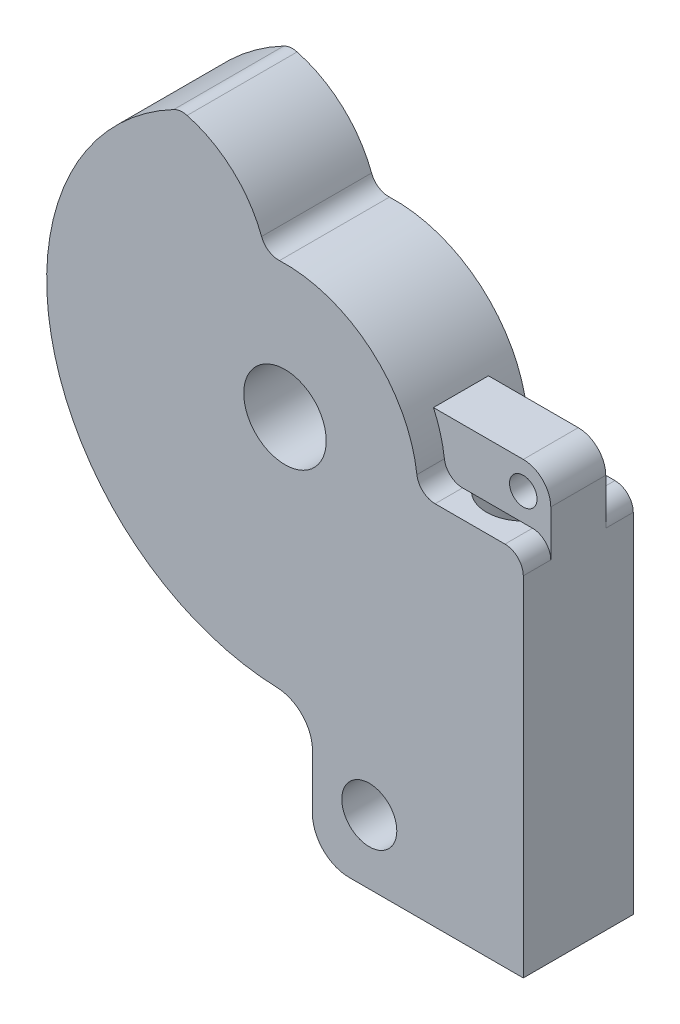
SolidWorks part; units mm, degrees
ref_plane "Front Plane" through (0, 0, 0) normal (0, 0, 1) x (1, 0, 0)
ref_plane "Top Plane" through (0, 0, 0) normal (0, 1, 0) x (1, 0, 0)
ref_plane "Right Plane" through (0, 0, 0) normal (1, 0, 0) x (0, 0, -1)
sketch "Sketch2" plane through (0, 0, 0) normal (0, 0, 1) x (1, 0, 0)
  line L0 (13, 0) -> (13, -20)
  line L1 (13, -20) -> (7, -20)
  line L2 (7, -20) -> (7, -10.9545)
  line L3 (10, 0) -> (10, -20) construction
  arc A0 (13, 0) -> (7, -10.9545) centre (0, 0) ccw
  circle A1 centre (0, 0) radius 10 construction
  dimension "Diameter" = 20
  dimension "Rod Holer Thickness" = 6
  dimension "Rod Holder Length" = 20
extrude "Boss-Extrude1" add sketch "Sketch2" along normal mid plane 6
hole_wizard "M4 Clearance Hole1" positions "Sketch3" profile "Sketch4" hole size "M4" standard "ANSI Metric" end condition up to next
sketch "Sketch3" plane through (0, 0, 3) normal (0, 0, 1) x (1, 0, 0)
  point P2 (0, 0)
sketch "Sketch4" plane through (0, 0, 3) normal (1, 0, 0) x (0, -1, 0)
  line L0 (0, 0) -> (0, 6)
  line L1 (0, 6) -> (2.25, 6)
  line L2 (2.25, 6) -> (2.25, 0)
  line L5 (2.25, 0) -> (0, 0)
  line L11 (0, -6.35) -> (0, 107.95) construction
  dimension "Thru Hole Dia." = 4.5
  dimension "Thru Hole Depth" = 6
sketch "Sketch5" plane through (0, -20, 0) normal (0, -1, 0) x (1, 0, 0)
  line L0 (13, 3) -> (7, -3) construction
  circle A0 centre (10, 0) radius 2
  dimension "Rod Hole Diameter" = 4
extrude "Cut-Extrude1" cut sketch "Sketch5" against normal blind 20
ref_axis "Axis1" through (10, 0, 0) along (0, -1, 0)
sketch "Sketch8" plane through (0, 0, -3) normal (0, 0, 1) x (1, 0, 0)
  line L0 (0, 0) -> (-21.8723, 0) construction
  line L1 (0, 0) -> (-6.8944, 5.7851) construction
  circle A0 centre (-6.8944, 5.7851) radius 3
  dimension "D2" = 6
  dimension "D1" = 40
  dimension "D3" = 9
extrude "Cut-Extrude3" cut sketch "Sketch8" along normal offset from surface (4.4 mm away) 1.6 up to face at (2.25, 0, 3)
sketch "Sketch9" plane through (0, 0, 3) normal (0, 0, 1) x (1, 0, 0)
  line L1 (13, 0) -> (7.25, 0)
  line L2 (13, 0) -> (13, 10.075) construction
  arc A0 (13, 0) -> (7, -10.9545) centre (0, 0) ccw construction
  arc A1 (7.25, 0) -> (-1.057, 7.1725) centre (0, 0) ccw
  circle A2 centre (0, 0) radius 2.25 construction
  arc A4 (-1.057, 7.1725) -> (-5.7272, 11.6705) centre (-6.8944, 5.7851) ccw
  circle A5 centre (-6.8944, 5.7851) radius 3 construction
  arc A6 (13, 0) -> (-5.7272, 11.6705) centre (0, 0) ccw
  dimension "D1" = 5
  dimension "D2" = 3
extrude "Cut-Extrude4" cut sketch "Sketch9" against normal through all
sketch "Sketch6" plane through (0, 0, 0) normal (0, 0, 1) x (1, 0, 0)
  line L4 (13, 1.5) -> (13, 0)
  line L6 (11.5, 3) -> (6.6002, 3)
  line L8 (7.25, 0) -> (13, 0) construction
  line L9 (7.25, 0) -> (13, 0)
  arc A2 (13, 1.5) -> (11.5, 3) centre (11.5, 1.5) ccw
  arc A3 (7.25, 0) -> (-1.057, 7.1725) centre (0, 0) ccw construction
  arc A4 (7.25, 0) -> (6.6002, 3) centre (0, 0) ccw
  dimension "Spring Attchment Diameter" = 1.5
extrude "Boss-Extrude2" add sketch "Sketch6" along normal mid plane 3
fillet "Fillet1" radius 1 6 edges at (-5.7272, 11.6705, 0) (7.25, 0, 2.25) (7.25, 0, -2.25) (-1.057, 7.1725, 0) (13, 0, -2.25) (13, 0, 2.25)
sketch "Sketch7" plane through (0, 0, 1.5) normal (0, 0, 1) x (1, 0, 0)
  circle A0 centre (11.5, 1.5) radius 0.75
  arc A1 (13, 1.5) -> (11.5, 3) centre (11.5, 1.5) ccw construction
  dimension "Spring Hole Diam" = 1.5
extrude "Cut-Extrude2" cut sketch "Sketch7" against normal through all both and the other way through all
fillet "Fillet2" [suppressed] radius 4
sketch "Sketch10" plane through (0, 0, -3) normal (0, 0, -1) x (-1, 0, 0)
  line L0 (-7, -10.9545) -> (-7, -20) construction
  line L1 (-7, -10.9545) -> (-7, -20)
  line L2 (-7, -20) -> (-1.5, -20)
  line L3 (-1.5, -20) -> (-1.5, -12.9132)
  arc A0 (-7, -10.9545) -> (6.0647, 11.4987) centre (0, 0) ccw construction
  arc A1 (-7, -10.9545) -> (-1.5, -12.9132) centre (0, 0) ccw
  circle A2 centre (-4.6, -16.5) radius 1.5
  dimension "D1" = 3
  dimension "D3" = 2
  dimension "D4" = 1.6
  dimension "D2" = 5.5
extrude "Boss-Extrude3" add sketch "Sketch10" against normal up to surface (6 mm away) up to face at (2.25, 0, 3)
fillet "Fillet3" radius 2 2 edges at (1.5, -12.9132, 0) (1.5, -20, 0)
